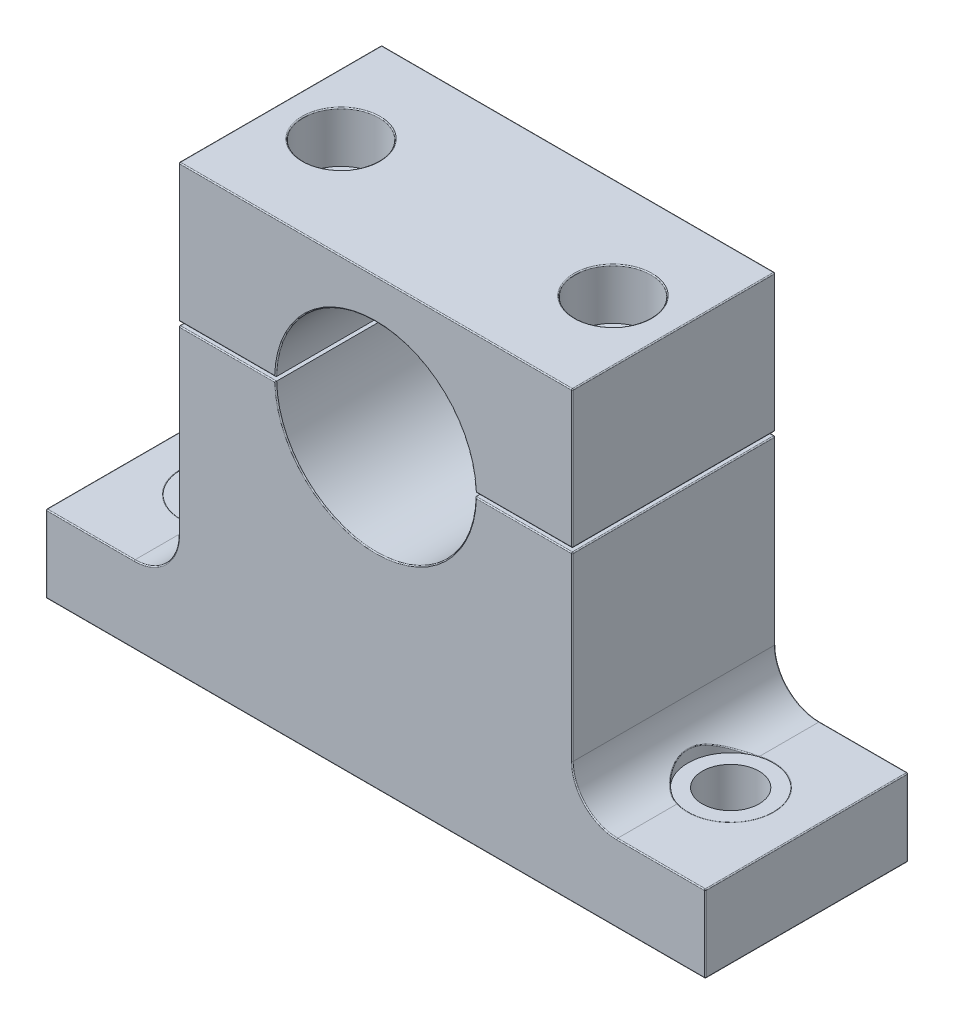
SolidWorks part; units mm, degrees
note: '?' marks a value the reader was unsure of.
material "ABS"
ref_plane "Front Plane" through (0, 0, 0) normal (0, 0, 1) x (1, 0, 0)
ref_plane "Top Plane" through (0, 0, 0) normal (0, 1, 0) x (1, 0, 0)
ref_plane "Right Plane" through (0, 0, 0) normal (1, 0, 0) x (0, 0, -1)
sketch "Sketch1" plane through (0, 0, 0) normal (0, 0, 1) x (1, 0, 0)
  line L0 (0, 17.4625) -> (0, -38.1) construction
  line L1 (41.275, -38.1) -> (-41.275, -38.1) construction
  line L2 (-24.638, 17.4625) -> (24.638, 17.4625) construction
  line L3 (0, 0.25) -> (0, -0.25) construction
  line L4 (-17.018, 0) -> (17.018, 0) construction
  line L5 (-31.75, -28.448) -> (31.75, -28.448) construction
  line L6 (-17.018, 17.4625) -> (-17.018, -38.1) construction
  line L7 (-21.7805, 17.4625) -> (-12.2555, 17.4625) construction
  line L8 (-20.193, -38.1) -> (-13.843, -38.1) construction
  line L9 (-35.306, -28.448) -> (-28.194, -28.448) construction
  line L10 (-37.084, -28.448) -> (-26.416, -28.448) construction
  circle A0 centre (0, 0) radius 12.5 construction
  point P7 (0, 0)
  point P8 (0, -38.1)
  point P11 (0, -28.448)
  point P14 (0, 17.4625)
  point P15 (0, 0)
  point P20 (0, -28.448)
  point P23 (-17.018, 11.1125)
  point P26 (-17.018, 17.4625)
  point P27 (-17.018, -38.1)
  point P30 (-31.75, -28.448)
  point P35 (-31.75, -28.448)
  dimension "D1" = 0.5
  dimension "D3" = 6.35
  dimension "D4" = 10.668
sketch "Sketch2" plane through (0, 0, 0) normal (0, 0, 1) x (1, 0, 0)
  line L0 (-24.638, 17.4625) -> (24.638, 17.4625)
  line L1 (41.275, -38.1) -> (-41.275, -38.1) construction
  line L2 (41.275, -38.1) -> (-41.275, -38.1)
  line L3 (-41.275, -38.1) -> (-41.275, -28.448)
  line L4 (-41.275, -28.448) -> (-30.1943, -28.448)
  line L5 (-24.638, -22.8918) -> (-24.638, -0.25)
  line L6 (24.638, 17.4625) -> (24.638, 0.25)
  line L7 (30.1943, -28.448) -> (41.275, -28.448)
  line L8 (41.275, -28.448) -> (41.275, -38.1)
  line L9 (-24.638, 0.25) -> (-12.4975, 0.25)
  line L10 (-24.638, -0.25) -> (-12.4975, -0.25)
  line L11 (-24.638, 0.25) -> (-24.638, 17.4625)
  line L12 (24.638, -0.25) -> (24.638, -22.8918)
  line L13 (12.4975, 0.25) -> (24.638, 0.25)
  line L14 (12.4975, -0.25) -> (24.638, -0.25)
  circle A0 centre (0, 0) radius 12.5 construction
  arc A1 (-12.4975, -0.25) -> (12.4975, -0.25) centre (0, 0) ccw
  arc A2 (12.4975, 0.25) -> (-12.4975, 0.25) centre (0, 0) ccw
  arc A3 (24.638, -22.8918) -> (30.1943, -28.448) centre (30.1943, -22.8918) ccw
  arc A4 (-30.1943, -28.448) -> (-24.638, -22.8918) centre (-30.1943, -22.8918) ccw
  dimension "D1" = 5.5562
extrude "Boss-Extrude1" add sketch "Sketch2" along normal mid plane 25.4
sketch "Sketch3" plane through (0, -28.448, 0) normal (0, 1, 0) x (1, 0, 0)
  line L0 (41.275, 0) -> (-41.275, 0) construction
  line L1 (-17.018, 0) -> (17.018, 0) construction
  circle A0 centre (-17.018, 0) radius 4.7625
  circle A1 centre (17.018, 0) radius 4.7625
  circle A2 centre (-31.75, 0) radius 3.556
  circle A3 centre (31.75, 0) radius 3.556
  circle A4 centre (-31.75, 0) radius 5.334 construction
  circle A5 centre (31.75, 0) radius 5.334 construction
  circle A6 centre (-17.018, 0) radius 4.7625 construction
  circle A9 centre (17.018, 0) radius 4.7625 construction
  point P6 (0, 0)
  point P16 (0, 0)
sketch "Sketch4" plane through (0, -28.448, 0) normal (0, 1, 0) x (1, 0, 0)
  circle A0 centre (-31.75, 0) radius 3.556 construction
  circle A1 centre (31.75, 0) radius 3.556 construction
  circle A2 centre (-31.75, 0) radius 3.556
  circle A3 centre (31.75, 0) radius 3.556
  point P0 (-31.75, 0)
extrude "Cut-Extrude1" cut sketch "Sketch4" against normal through all
sketch "Sketch5" plane through (0, -28.448, 0) normal (0, 1, 0) x (1, 0, 0)
  circle A0 centre (31.75, 0) radius 5.334 construction
  circle A1 centre (-31.75, 0) radius 5.334 construction
  circle A2 centre (31.75, 0) radius 5.334
  circle A3 centre (-31.75, 0) radius 5.334
extrude "Cut-Extrude2" cut sketch "Sketch5" against normal blind 0.02 and the other way through all
sketch "Sketch6" plane through (0, 17.4625, 0) normal (0, 1, 0) x (1, 0, 0)
  circle A0 centre (17.018, 0) radius 4.7625 construction
  circle A1 centre (-17.018, 0) radius 4.7625 construction
  circle A2 centre (17.018, 0) radius 4.7625
  circle A3 centre (-17.018, 0) radius 4.7625
extrude "Cut-Extrude3" cut sketch "Sketch6" against normal up to vertex (6.35 mm away) up to point (-17.018, 11.1125, 0)
sketch "Sketch8" plane through (0, 11.1125, 0) normal (0, 1, 0) x (1, 0, 0)
  circle A2 centre (17.018, 0) radius 3.175
  circle A3 centre (-17.018, 0) radius 3.175
extrude "Cut-Extrude4" cut sketch "Sketch8" against normal through all
sketch "Sketch10" plane through (0, 0, 0) normal (0, 0, 1) x (1, 0, 0)
  line L4 (-17.018, 17.4625) -> (-12.2555, 17.4625)
  line L5 (-12.2555, 17.4625) -> (-12.2555, 11.1125)
  line L6 (-12.2555, 11.1125) -> (-13.843, 11.1125)
  line L7 (-13.843, 11.1125) -> (-13.843, -38.1)
  line L10 (-13.843, -38.1) -> (-17.018, -38.1)
  line L11 (-17.018, -38.1) -> (-17.018, 17.4625)
revolve "Revolve1" [suppressed] add sketch "Sketch10" angle 360 about L11
sketch "Sketch11" [suppressed] plane through (0, 17.4625, 0) normal (0, 1, 0) x (1, 0, 0)
  line L1 (-17.018, 2.6396) -> (-19.304, 1.3198)
  line L2 (-19.304, 1.3198) -> (-19.304, -1.3198)
  line L3 (-19.304, -1.3198) -> (-17.018, -2.6396)
  line L4 (-17.018, -2.6396) -> (-14.732, -1.3198)
  line L5 (-14.732, -1.3198) -> (-14.732, 1.3198)
  line L6 (-14.732, 1.3198) -> (-17.018, 2.6396)
  circle A0 centre (-17.018, 0) radius 2.286 construction
  circle A1 centre (-17.018, 0) radius 4.7625 construction
  circle A2 centre (-17.018, 0) radius 4.7625 construction
  dimension "D1" = 9.525
  dimension "D2" = 4.572
extrude "Cut-Extrude5" [suppressed] cut sketch "Sketch11" against normal blind 3
chamfer "Chamfer1" [suppressed] distance 0.9525 angle 45
mirror "Mirror1" [suppressed] about plane through (0, 0, 0) normal (1, 0, 0)
fillet "Fillet1" radius 0.127 36 edges at (26.4412, -26.9889, -0.5175) (-26.4412, -26.9889, 0.5175) (28.194, -38.1, 0) (-35.306, -38.1, 0) (-20.193, -38.1, 0) (13.843, -38.1, 0) (41.275, -38.1, 0) (41.275, -28.448, 0) (24.638, -0.25, 0) (-24.638, -0.25, 0) (-41.275, -28.448, 0) (-41.275, -38.1, 0) (35.7346, -28.448, -12.7) (26.2654, -26.8206, -12.7) (24.638, -11.5709, -12.7) (18.5677, -0.25, -12.7) (0, -12.5, -12.7) (-18.5677, -0.25, -12.7) (-24.638, -11.5709, -12.7) (-26.2654, -26.8206, -12.7) (-35.7346, -28.448, -12.7) (-41.275, -33.274, -12.7) (0, -38.1, -12.7) (41.275, -33.274, -12.7) (0, -38.1, 12.7) (-41.275, -33.274, 12.7) (-35.7346, -28.448, 12.7) (-26.2654, -26.8206, 12.7) (-24.638, -11.5709, 12.7) (-18.5677, -0.25, 12.7) (0, -12.5, 12.7) (18.5677, -0.25, 12.7) (24.638, -11.5709, 12.7) (26.2654, -26.8206, 12.7) (35.7346, -28.448, 12.7) (41.275, -33.274, 12.7)
fillet "Fillet2" radius 0.127 18 edges at (24.638, 0.25, 0) (-18.5677, 0.25, -12.7) (0, 12.5, -12.7) (18.5677, 0.25, -12.7) (24.638, 8.8563, -12.7) (-24.638, 0.25, 0) (-24.638, 8.8563, -12.7) (24.638, 17.4625, 0) (-24.638, 17.4625, 0) (0, 17.4625, -12.7) (-21.7805, 17.4625, 0) (12.2555, 17.4625, 0) (0, 17.4625, 12.7) (24.638, 8.8563, 12.7) (18.5677, 0.25, 12.7) (0, 12.5, 12.7) (-18.5677, 0.25, 12.7) (-24.638, 8.8563, 12.7)
ref_plane "Contact Plane 1" through (0, -38.1, 0) normal (0, -1, 0) x (-1, 0, 0)
ref_axis "Center Axis 1" through (0, 0, 12.573) along (0, 0, -1)?
split "Split1" trim tools "Top Plane" bodies to split 109 110 resulting bodies 127 128
equation "\"D3@Sketch1\"=\"G@Sketch1\""
equation "\"D4@Sketch1\"=\"K@Sketch1\"*1.5"
equation "\"D2@Sketch11\"=\"D1@Sketch11\"*.48"
equation "\"D1@Sketch2\"=\"Height@Sketch1\"*.1"
equation "\"D1@Chamfer1\"=\"Screw Head Dia@Sketch1\"*.1"
